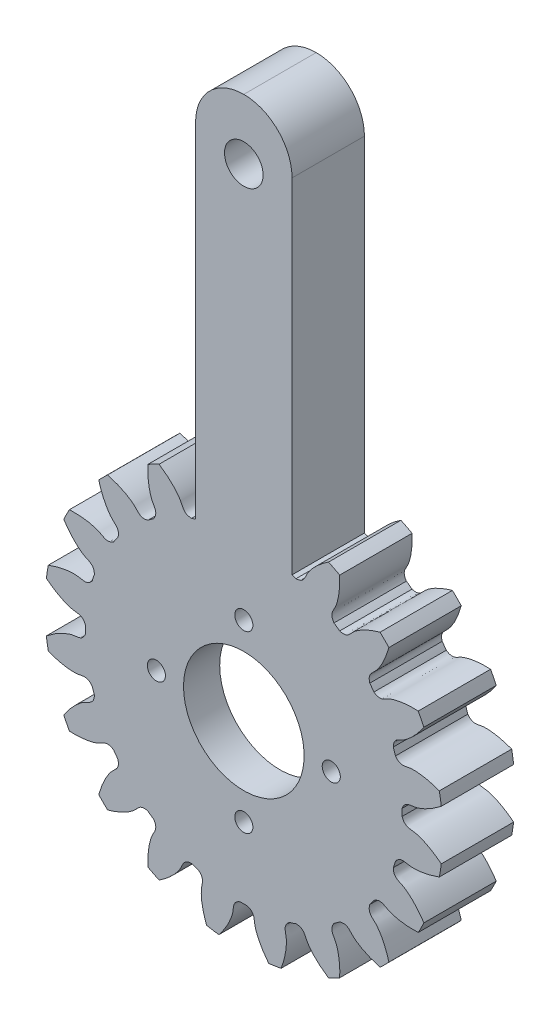
SolidWorks part; units mm, degrees
ref_plane "前视基准面" through (0, 0, 0) normal (0, 0, 1) x (1, 0, 0)
ref_plane "上视基准面" through (0, 0, 0) normal (0, 1, 0) x (1, 0, 0)
ref_plane "右视基准面" through (0, 0, 0) normal (1, 0, 0) x (0, 0, -1)
sketch "草图1" plane through (0, 0, 0) normal (0, 0, 1) x (1, 0, 0)
  circle A0 centre (0, 0) radius 16.5
extrude "凸台-拉伸1" add sketch "草图1" along normal blind 6
ref_axis "基准轴1" through (0, 0, -0.3) along (0, 0, 1)
sketch "草图2" plane through (0, 0, 0) normal (0, 0, 1) x (1, 0, 0)
  line L0 (0, 0) -> (0, 16.5) construction
  circle A0 centre (0, 0) radius 16.5 construction
  arc A1 (0.29, 13.1218) -> (-0.29, 13.1218) centre (0, 0) ccw
  arc A2 (4.7717, 18.7474) -> (-4.7717, 18.7474) centre (0, 0) ccw
  spline S0 degree 3 poles (0.29, 13.1218) (0.9168, 13.3402) (0.8356, 13.7807) (0.9193, 14.205) (0.9283, 14.2463) (0.9395, 14.293) (0.9529, 14.3448) (0.969, 14.4018) (0.9878, 14.4638) (1.0095, 14.5309) (1.0345, 14.6028) (1.0629, 14.6795) (1.0948, 14.7608) (1.1305, 14.8467) (1.1702, 14.9371) (1.2141, 15.0317) (1.2623, 15.1305) (1.315, 15.2334) (1.3725, 15.3401) (1.4349, 15.4506) (1.5023, 15.5646) (1.575, 15.6821) (1.653, 15.8029) (1.7366, 15.9267) (1.826, 16.0534) (1.9211, 16.1829) (2.0223, 16.3149) (2.1296, 16.4493) (2.2432, 16.5859) (2.3632, 16.7244) (2.4897, 16.8646) (2.6229, 17.0065) (2.7628, 17.1496) (2.9095, 17.2939) (3.0632, 17.4391) (3.224, 17.585) (3.3918, 17.7313) (3.567, 17.8779) (3.7493, 18.0245) (3.9391, 18.1709) (4.1363, 18.3167) (4.4122, 18.5125) (4.6259, 18.6545) (4.7717, 18.7474) knots 0 0 0 0 0.165916 0.170906 0.176664 0.183189 0.190482 0.198542 0.207371 0.216967 0.22733 0.238462 0.250361 0.263027 0.276462 0.290664 0.305634 0.321371 0.337876 0.355149 0.37319 0.391998 0.411574 0.431917 0.453028 0.474907 0.497554 0.520968 0.54515 0.570099 0.595817 0.622302 0.649554 0.677575 0.706363 0.735918 0.766242 0.797333 0.829191 0.861818 0.895212 0.929373 1 1 1 1
  spline S1 degree 3 poles (-0.29, 13.1218) (-0.9168, 13.3402) (-0.8356, 13.7807) (-0.9193, 14.205) (-0.9283, 14.2463) (-0.9395, 14.293) (-0.9529, 14.3448) (-0.969, 14.4018) (-0.9878, 14.4638) (-1.0095, 14.5309) (-1.0345, 14.6028) (-1.0629, 14.6795) (-1.0948, 14.7608) (-1.1305, 14.8467) (-1.1702, 14.9371) (-1.2141, 15.0317) (-1.2623, 15.1305) (-1.315, 15.2334) (-1.3725, 15.3401) (-1.4349, 15.4506) (-1.5023, 15.5646) (-1.575, 15.6821) (-1.653, 15.8029) (-1.7366, 15.9267) (-1.826, 16.0534) (-1.9211, 16.1829) (-2.0223, 16.3149) (-2.1296, 16.4493) (-2.2432, 16.5859) (-2.3632, 16.7244) (-2.4897, 16.8646) (-2.6229, 17.0065) (-2.7628, 17.1496) (-2.9095, 17.2939) (-3.0632, 17.4391) (-3.224, 17.585) (-3.3918, 17.7313) (-3.567, 17.8779) (-3.7493, 18.0245) (-3.9391, 18.1709) (-4.1363, 18.3167) (-4.4122, 18.5125) (-4.6259, 18.6545) (-4.7717, 18.7474) knots 0 0 0 0 0.165916 0.170906 0.176664 0.183189 0.190482 0.198542 0.207371 0.216967 0.22733 0.238462 0.250361 0.263027 0.276462 0.290664 0.305634 0.321371 0.337876 0.355149 0.37319 0.391998 0.411574 0.431917 0.453028 0.474907 0.497554 0.520968 0.54515 0.570099 0.595817 0.622302 0.649554 0.677575 0.706363 0.735918 0.766242 0.797333 0.829191 0.861818 0.895212 0.929373 1 1 1 1
extrude "切除-拉伸1" cut sketch "草图2" along normal through all
pattern_circular "阵列(圆周)1" count 20 every 18 about axis through (0, 0, -0.3) along (0, 0, 1) of "切除-拉伸1"
sketch "草图3" plane through (0, 0, 0) normal (0, 0, 1) x (1, 0, 0)
  circle A0 centre (0, 0) radius 15 construction
  dimension "Dn" = 30
sketch "草图5" plane through (0, 0, 0) normal (0, 0, -1) x (-1, 0, 0)
  circle A0 centre (0, 0) radius 10.75
  dimension "D1" = 21.5
extrude "切除-拉伸2" cut sketch "草图5" against normal blind 3
sketch "草图6" plane through (0, 0, 3) normal (0, 0, -1) x (-1, 0, 0)
  circle A0 centre (0, 0) radius 5
  dimension "D1" = 10
extrude "切除-拉伸3" cut sketch "草图6" against normal blind 3
sketch "草图7" plane through (0, 0, 3) normal (0, 0, -1) x (-1, 0, 0)
  line L0 (3.3, 0) -> (-3.3, 0) construction
  line L1 (0, 3.3) -> (0, -3.3) construction
  circle A0 centre (0, 7.25) radius 0.75
  circle A1 centre (7.25, 0) radius 0.75
  circle A2 centre (0, -7.25) radius 0.75
  circle A3 centre (-7.25, 0) radius 0.75
  dimension "D3" = 1.5
  dimension "D4" = 1.5
  dimension "D1" = 7.25
  dimension "D2" = 7.25
extrude "切除-拉伸4" cut sketch "草图7" against normal blind 3
sketch "草图8" plane through (0, 0, 0) normal (0, 0, -1) x (-1, 0, 0)
  line L0 (0, 0) -> (0, 23.1948) construction
  line L2 (-4, 50) -> (4, 50)
  line L3 (-4, 50) -> (-4, 11.5651)
  line L4 (-4, 11.5651) -> (4, 11.5651)
  line L5 (4, 50) -> (4, 11.5651)
  line L6 (-4, 50) -> (4, 11.5651) construction
  line L7 (-4, 11.5651) -> (4, 50) construction
  point P3 (0, 30.7826)
  dimension "D1" = 8
  dimension "D2" = 50
extrude "凸台-拉伸2" add sketch "草图8" against normal up to surface (6 mm away) up to face at (-0.75, 7.25, 6)
sketch "草图9" plane through (0, 0, 0) normal (0, 0, -1) x (-1, 0, 0)
  line L0 (4, 12.5006) -> (4, 50) construction
  line L1 (-4, 50) -> (4, 50)
  line L2 (-4, 50) -> (-4, 45)
  line L3 (-4, 45) -> (4, 45)
  line L4 (4, 50) -> (4, 45)
  circle A0 centre (0, 40) radius 1.6
  dimension "D3" = 3.2
  dimension "D1" = 40
  dimension "D2" = 5
extrude "切除-拉伸5" cut sketch "草图9" against normal blind 10
fillet "圆角1" radius 4 2 edges at (4, 45, 3) (-4, 45, 3)
